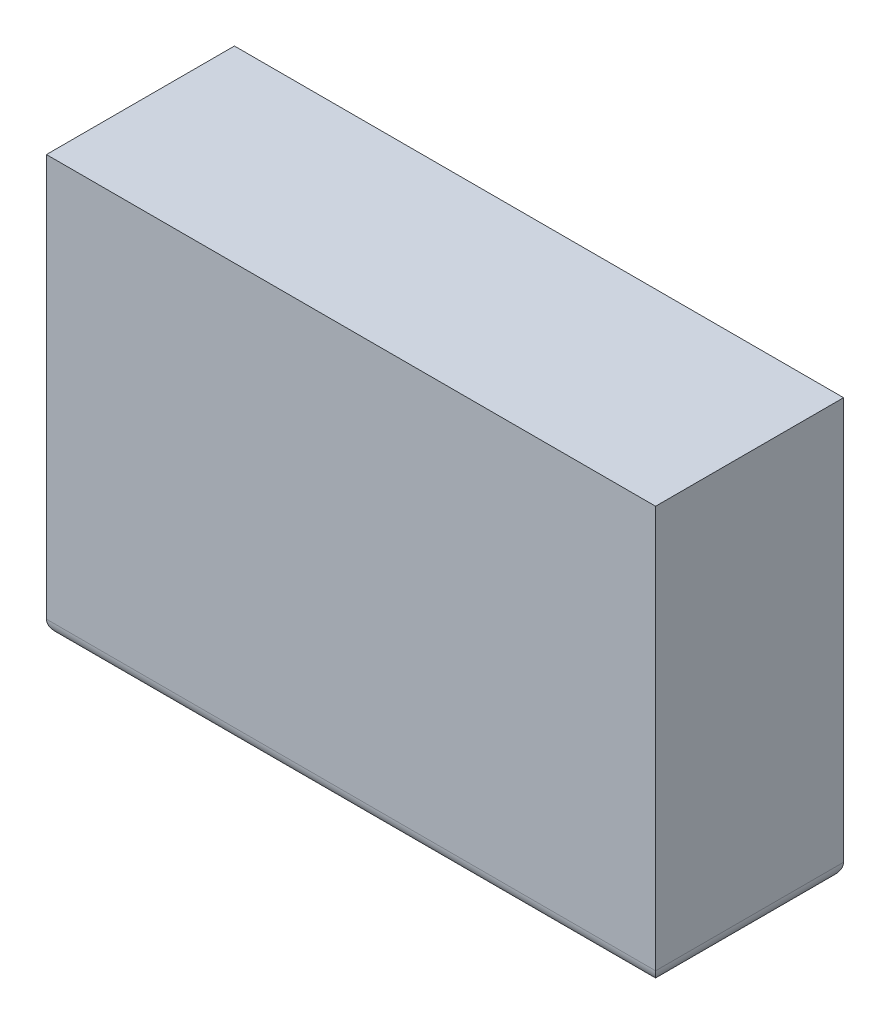
SolidWorks part; units mm, degrees
material "ABS PC"
ref_plane "Front Plane" through (0, 0, 0) normal (0, 0, 1) x (1, 0, 0)
ref_plane "Top Plane" through (0, 0, 0) normal (0, 1, 0) x (1, 0, 0)
ref_plane "Right Plane" through (0, 0, 0) normal (1, 0, 0) x (0, 0, -1)
sketch "Sketch1" plane through (0, 0, 0) normal (0, 1, 0) x (1, 0, 0)
  line L0 (-81, 33.5504) -> (81, 33.5504)
  line L1 (-77, -12.4496) -> (77, -12.4496)
  line L2 (-77, -12.4496) -> (-77, 29.5504)
  line L3 (-77, 29.5504) -> (77, 29.5504)
  line L4 (77, -12.4496) -> (77, 29.5504)
  line L5 (-77, -12.4496) -> (77, 29.5504) construction
  line L6 (-77, 29.5504) -> (77, -12.4496) construction
  line L7 (81, -16.4496) -> (81, 33.5504)
  line L8 (-81, -16.4496) -> (81, -16.4496)
  line L9 (-81, -16.4496) -> (-81, 33.5504)
  circle A0 centre (-57, 8.5504) radius 5
  circle A1 centre (57, 8.5504) radius 5
  point P0 (0, 0)
  dimension "D3" = 20
  dimension "D1" = 154
  dimension "D2" = 42
  dimension "D4" = 20
  dimension "D5" = 4
extrude "Boss-Extrude1" add sketch "Sketch1" against normal blind 10 contours A0 | A1 region at (-57, 0, -8.5504) region at (57, 0, -8.5504)
extrude "Boss-Extrude2" add sketch "Sketch1<3>" along normal blind 4 contours L1 L4 L3 L2 A1 A0 | L9 L8 L7 L0 L4 L1 L2 L3 | A0 | A1 region at (0, 0, -31.855) region at (0, 0, -8.5504) region at (-57, 0, -8.5504) region at (57, 0, -8.5504)
sketch "Sketch1<3>" plane through (0, 0, 0) normal (0, 1, 0) x (1, 0, 0) same geometry as "Sketch1"
extrude "Boss-Extrude3" add sketch "Sketch1<4>" along normal blind 96 contours L9 L8 L7 L0 L4 L1 L2 L3 region at (0, 0, -31.855)
sketch "Sketch1<4>" plane through (0, 0, 0) normal (0, 1, 0) x (1, 0, 0) same geometry as "Sketch1"
fillet "Fillet1" radius 4 4 edges at (0, 0, -33.5504) (-81, 0, -8.5504) (81, 0, -8.5504) (0, 0, 16.4496)
sketch "Sketch2" plane through (0, 96, 0) normal (0, 1, 0) x (1, 0, 0)
  line L1 (-81, -16.4496) -> (81, -16.4496)
  line L2 (-81, -16.4496) -> (-81, 33.5504)
  line L3 (-81, 33.5504) -> (81, 33.5504)
  line L4 (81, -16.4496) -> (81, 33.5504)
  line L5 (-77, -12.4496) -> (77, -12.4496)
  line L6 (-77, -12.4496) -> (-77, 29.5504)
  line L7 (-77, 29.5504) -> (77, 29.5504)
  line L8 (77, -12.4496) -> (77, 29.5504)
extrude "Boss-Extrude4" add sketch "Sketch2" along normal blind 5 separate body
extrude "Boss-Extrude5" add sketch "Sketch2<2>" along normal blind 5
sketch "Sketch2<2>" plane through (0, 96, 0) normal (0, 1, 0) x (1, 0, 0) same geometry as "Sketch2"
sketch "Sketch3" plane through (0, 0, -33.5504) normal (0, 0, -1) x (-1, 0, 0)
  circle A0 centre (0, 53.4883) radius 5
extrude "Cut-Extrude1" cut sketch "Sketch3" against normal blind 10
sketch "Sketch4" plane through (0, 101, 0) normal (0, 1, 0) x (1, 0, 0)
  line L1 (-81, 33.5504) -> (81, 33.5504)
  line L2 (-81, 33.5504) -> (-81, -16.4496)
  line L3 (-81, -16.4496) -> (81, -16.4496)
  line L4 (81, 33.5504) -> (81, -16.4496)
extrude "Boss-Extrude6" add sketch "Sketch4" along normal blind 10
